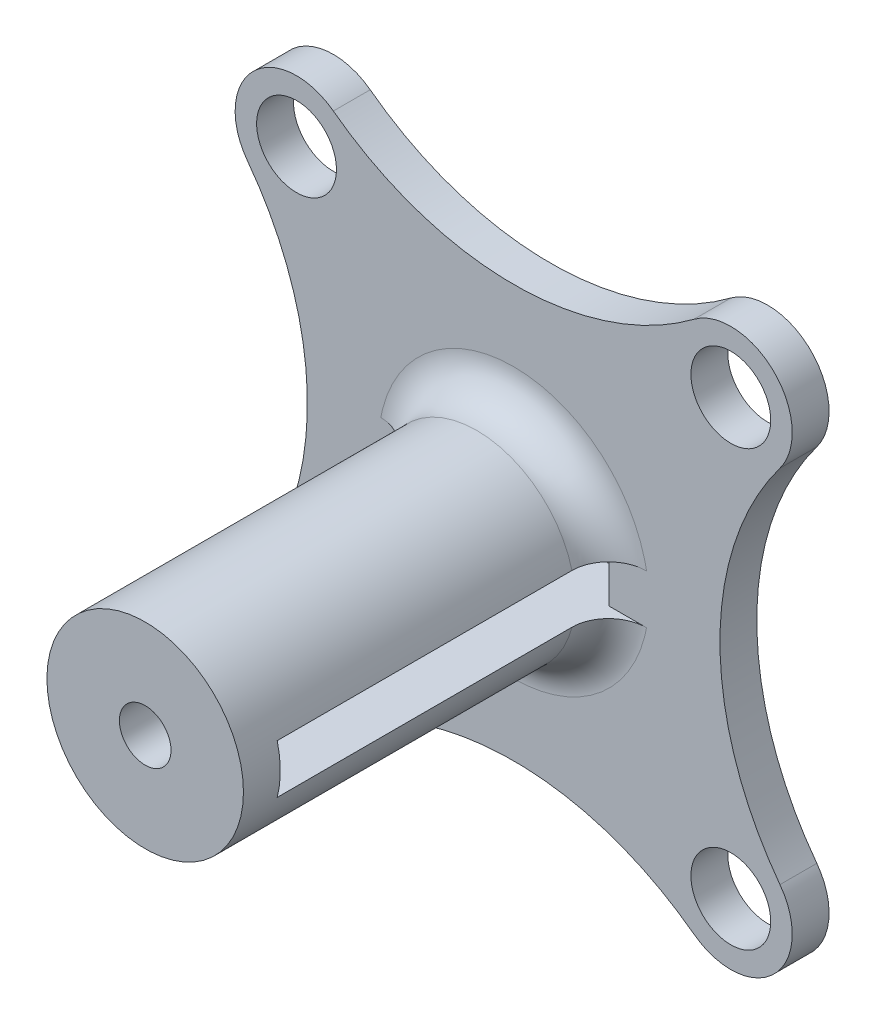
SolidWorks part; units mm, degrees
ref_plane "Alzado" through (0, 0, 0) normal (0, 0, 1) x (1, 0, 0)
ref_plane "Planta" through (0, 0, 0) normal (0, 1, 0) x (1, 0, 0)
ref_plane "Vista lateral" through (0, 0, 0) normal (1, 0, 0) x (0, 0, -1)
sketch "Croquis1" plane through (0, 0, 0) normal (0, 0, 1) x (1, 0, 0)
  arc A1 (-14.6812, 21.6803) -> (-21.6803, 14.6812) centre (-17.6777, 17.6777) ccw
  circle A2 centre (-17.6777, 17.6777) radius 3.25
  circle A3 centre (-17.6777, 17.6777) radius 3.25 construction
  circle A5 centre (17.6777, 17.6777) radius 3.25
  arc A6 (14.6812, -21.6803) -> (21.6803, -14.6812) centre (17.6777, -17.6777) ccw
  circle A7 centre (17.6777, -17.6777) radius 3.25
  circle A9 centre (-17.6777, -17.6777) radius 3.25
  arc A10 (-21.6803, 14.6812) -> (-21.6803, -14.6812) centre (-41.2912, 0) cw
  arc A12 (14.6812, 21.6803) -> (-14.6812, 21.6803) centre (0, 41.2912) cw
  arc A13 (21.6803, -14.6812) -> (21.6803, 14.6812) centre (41.2912, 0) cw
  arc A14 (-14.6812, -21.6803) -> (14.6812, -21.6803) centre (0, -41.2912) cw
  circle A16 centre (0, 0) radius 25 construction
  circle A19 centre (0, 0) radius 41.2912 construction
  arc A20 (-21.6803, -14.6812) -> (-14.6812, -21.6803) centre (-17.6777, -17.6777) ccw
  arc A34 (21.6803, 14.6812) -> (14.6812, 21.6803) centre (17.6777, 17.6777) ccw
  point P21 (0, 0)
  point P42 (0, 0)
  dimension "D1" = 24.4975
  dimension "D5" = 5
  dimension "D3" = 17.6777
  dimension "D4" = 17.6777
  dimension "D2" = 41.2912
  dimension "D6" = 4
extrude "Saliente-Extruir1" add sketch "Croquis1" along normal blind 3 contours A9 | A6 A7 | A5 | A1 A2 region at (0, 0, 0)
sketch "Croquis2" plane through (0, 0, 3) normal (0, 0, 1) x (1, 0, 0)
  line L12 (3, -6.65) -> (3, -2)
  line L13 (-3, -6.65) -> (3, -6.65)
  line L14 (-3, -2) -> (-3, -6.65)
  line L15 (-7.746, -2) -> (-3, -2)
  line L16 (-7.746, 2) -> (-7.746, -2)
  line L17 (-3, 2) -> (-7.746, 2)
  line L18 (-3, 6.65) -> (-3, 2)
  line L19 (3, 6.65) -> (-3, 6.65)
  line L20 (3, 2) -> (3, 6.65)
  line L21 (7.746, 2) -> (3, 2)
  line L22 (7.746, -2) -> (7.746, 2)
  line L23 (3, -2) -> (7.746, -2)
  line L24 (3, -6.65) -> (3, -2)
  line L25 (-3, -6.65) -> (3, -6.65)
  line L26 (-3, -2) -> (-3, -6.65)
  line L27 (-7.746, -2) -> (-3, -2)
  line L28 (-7.746, 2) -> (-7.746, -2)
  line L29 (-3, 2) -> (-7.746, 2)
  line L30 (-3, 6.65) -> (-3, 2)
  line L31 (3, 6.65) -> (-3, 6.65)
  line L32 (3, 2) -> (3, 6.65)
  line L33 (7.746, 2) -> (3, 2)
  line L34 (7.746, -2) -> (7.746, 2)
  line L35 (3, -2) -> (7.746, -2)
  dimension "D2" = 0
extrude "Cortar-Extruir2" cut sketch "Croquis2" against normal up to next
sketch "Croquis3" plane through (0, 0, 3) normal (0, 0, 1) x (1, 0, 0)
  line L13 (3, -6.65) -> (3, -2)
  line L14 (-3, -6.65) -> (3, -6.65)
  line L15 (-3, -2) -> (-3, -6.65)
  line L16 (-7.746, -2) -> (-3, -2)
  line L17 (-7.746, 2) -> (-7.746, -2)
  line L18 (-3, 2) -> (-7.746, 2)
  line L19 (-3, 6.65) -> (-3, 2)
  line L20 (3, 6.65) -> (-3, 6.65)
  line L21 (3, 2) -> (3, 6.65)
  line L22 (7.746, 2) -> (3, 2)
  line L23 (7.746, -2) -> (7.746, 2)
  line L24 (3, -2) -> (7.746, -2)
  line L25 (3, -6.65) -> (3, -2)
  line L26 (-3, -6.65) -> (3, -6.65)
  line L27 (-3, -2) -> (-3, -6.65)
  line L28 (-7.746, -2) -> (-3, -2)
  line L29 (-7.746, 2) -> (-7.746, -2)
  line L30 (-3, 2) -> (-7.746, 2)
  line L31 (-3, 6.65) -> (-3, 2)
  line L32 (3, 6.65) -> (-3, 6.65)
  line L33 (3, 2) -> (3, 6.65)
  line L34 (7.746, 2) -> (3, 2)
  line L35 (7.746, -2) -> (7.746, 2)
  line L36 (3, -2) -> (7.746, -2)
  circle A0 centre (0, 0) radius 8
  line M14 (7.746, -2) -> (3, -2)
  line M15 (3, -2) -> (3, -6.65)
  line M16 (3, -6.65) -> (-3, -6.65)
  line M17 (-3, -6.65) -> (-3, -2)
  line M18 (-3, -2) -> (-7.746, -2)
  line M20 (-7.746, 2) -> (-3, 2)
  line M21 (-3, 2) -> (-3, 6.65)
  line M22 (-3, 6.65) -> (3, 6.65)
  line M23 (3, 6.65) -> (3, 2)
  line M24 (3, 2) -> (7.746, 2)
  dimension "D2" = 0
extrude "Saliente-Extruir2" add sketch "Croquis3" along normal blind 30 contours A0 M24 M20 M21 M22 M23 | A0 M18 M14 M15 M16 M17 region at (3.1661, -4.325, 3) region at (5.373, 2.1661, 3)
sketch "Croquis4" plane through (0, 0, 33) normal (0, 0, 1) x (1, 0, 0)
  circle A0 centre (0, 0) radius 8
  circle A1 centre (0, 0) radius 2.1
  dimension "D1" = 16
  dimension "D2" = 4.2
extrude "Saliente-Extruir3" add sketch "Croquis4" against normal blind 3
fillet "Redondeo1" radius 3 2 edges at (0, -8, 3) (0, 8, 3)
